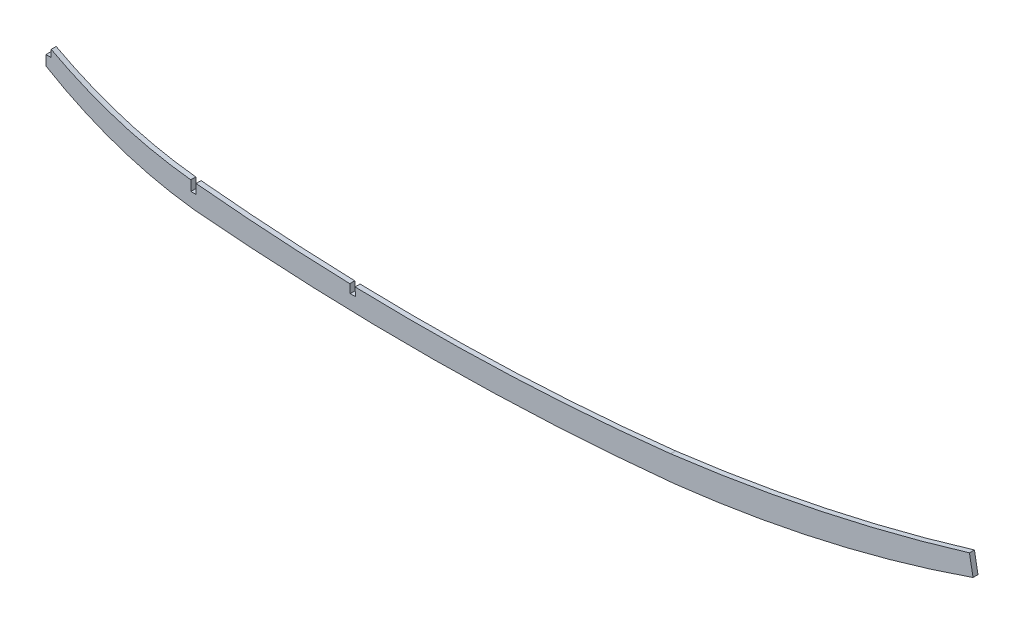
SolidWorks part; units mm, degrees
material "Balsa"
ref_plane "Front Plane" through (0, 0, 0) normal (0, 0, 1) x (1, 0, 0)
ref_plane "Top Plane" through (0, 0, 0) normal (0, 1, 0) x (1, 0, 0)
ref_plane "Right Plane" through (0, 0, 0) normal (1, 0, 0) x (0, 0, -1)
sketch "Sketch2" plane through (0, 0, 0) normal (0, 0, 1) x (1, 0, 0)
  line L0 (0, -94.4694) -> (0, -81.7694)
  line L1 (0, -94.4694) -> (93.98, -94.4694) construction
  line L2 (93.98, -126.4975) -> (93.98, -111.2575) construction
  line L3 (349.6407, -137.6462) -> (348.9613, -137.618) construction
  line L4 (349.6407, -137.6462) -> (354.8905, -137.8645) construction
  line L5 (93.98, -94.4694) -> (93.98, -126.4975) construction
  line L6 (400.2036, -124.7658) -> (400.2036, -94.4694) construction
  line L7 (590.8643, -81.3536) -> (588.5933, -68.8583)
  line L8 (0, 0) -> (672.417, 0) construction
  line L10 (93.98, -94.4694) -> (590.8643, -94.4694) construction
  line L11 (590.8643, -94.4694) -> (590.8643, -81.3536) construction
  line L12 (400.2036, -124.7658) -> (396.2207, -94.4694) construction
  arc A0 (0, -94.4694) -> (93.98, -126.4975) centre (121.7349, 108.8411) ccw
  arc A3 (93.98, -126.4975) -> (400.2036, -124.7658) centre (237.9716, 1487.1243) ccw
  arc A6 (400.2036, -124.7658) -> (590.8643, -81.3536) centre (300.4984, 753.5129) ccw
  arc A7 (93.98, -111.2575) -> (398.1841, -109.4039) centre (237.3586, 1321.3743) ccw
  arc A10 (0, -81.7694) -> (93.98, -111.2575) centre (118.1544, 130.2915) ccw
  arc A11 (398.1841, -109.4039) -> (588.5933, -68.8583) centre (254.6725, 1031.9221) ccw
  dimension "D3" = 236.9696
  dimension "D4" = 30.2963
  dimension "D5" = 400.2036
  dimension "D6" = 79.699
  dimension "D7" = 82.511
  dimension "D8" = 15.24
  dimension "D11" = 242.7557
  dimension "D14" = 1620.0336
  dimension "D15" = 883.92
  dimension "D16" = 15.494
  dimension "D18" = 1150.3133
  dimension "D1" = 12.7
  dimension "D2" = 81.7694
  dimension "D9" = 32.028
  dimension "D10" = 93.98
  dimension "D12" = 13.1158
  dimension "D13" = 496.8843
  dimension "D17" = 12.7
extrude "Boss-Extrude1" add sketch "Sketch2" along normal blind 3.175 contours A11 A7 A10 L0 A0 A3 A6 region at (5.9433, -88.1194, 0)
sketch "Sketch3" plane through (0, 0, 3.175) normal (0, 0, 1) x (1, 0, 0)
  line L0 (0, 0) -> (0, -81.8237) construction
  line L1 (0, 0) -> (93.98, 0) construction
  line L2 (93.98, 0) -> (93.98, -117.6075) construction
  line L4 (0, -81.8237) -> (0, -88.0975)
  line L5 (0, -88.0975) -> (3.302, -88.0975)
  line L6 (3.302, -81.8237) -> (3.302, -88.0975)
  line L7 (193.9543, -123.223) -> (197.1266, -123.0902)
  line L8 (0, -81.8237) -> (0, -80.8493)
  line L9 (0, -80.8493) -> (3.302, -80.8493)
  line L10 (3.302, -80.8493) -> (3.302, -81.8237)
  line L11 (186.3309, 134.7479) -> (183.1587, 134.6151)
  line L12 (92.2909, -117.5313) -> (95.6691, -117.5313)
  line L13 (92.2909, -117.5313) -> (92.2909, -108.4147)
  line L14 (92.2909, -108.4147) -> (95.6691, -108.4147)
  line L15 (95.6691, -117.5313) -> (95.6691, -108.4147)
  line L16 (193.687, -116.8375) -> (196.8592, -116.7047)
  line L17 (186.5983, 128.3624) -> (183.4261, 128.2296)
  line L18 (197.1266, -123.0902) -> (196.8592, -116.7047)
  line L19 (186.5983, 128.3624) -> (186.3309, 134.7479)
  line L20 (193.9543, -123.223) -> (193.687, -116.8375)
  line L21 (183.4261, 128.2296) -> (183.1587, 134.6151)
  line L22 (183.4261, 128.2296) -> (183.1587, 134.6151)
  line L24 (186.5983, 128.3624) -> (186.3309, 134.7479)
  line L26 (186.5983, 128.3624) -> (183.4261, 128.2296)
  line L28 (186.3309, 134.7479) -> (183.1587, 134.6151)
  line L30 (195.5404, -123.1566) -> (190.3839, 0) construction
  line L31 (93.98, 0) -> (229.0313, 0) construction
  line L33 (193.8496, -123.1511) -> (197.2249, -123.0098)
  line L34 (193.8496, -123.1511) -> (193.5511, -116.0212)
  line L35 (197.2249, -123.0098) -> (196.9263, -115.8799)
  line L36 (193.5511, -116.0212) -> (196.9263, -115.8799)
  point P14 (93.98, -108.4147)
  point P25 (195.2387, -115.9505)
  point P26 (195.5404, -123.1566)
  point P31 (0, 0)
  dimension "D1" = 81.8237
  dimension "D2" = 6.2738
  dimension "D3" = 3.302
  dimension "D4" = 93.98
  dimension "D5" = 117.6075
  dimension "D6" = 3.3782
  dimension "D7" = 0.0762
  dimension "D8" = 92.398
  dimension "D9" = 0.0762
  dimension "D10" = 3.3782
  dimension "D11" = 190.3839
  dimension "D12" = 123.2645
extrude "Cut-Extrude2" cut sketch "Sketch3" against normal through all
